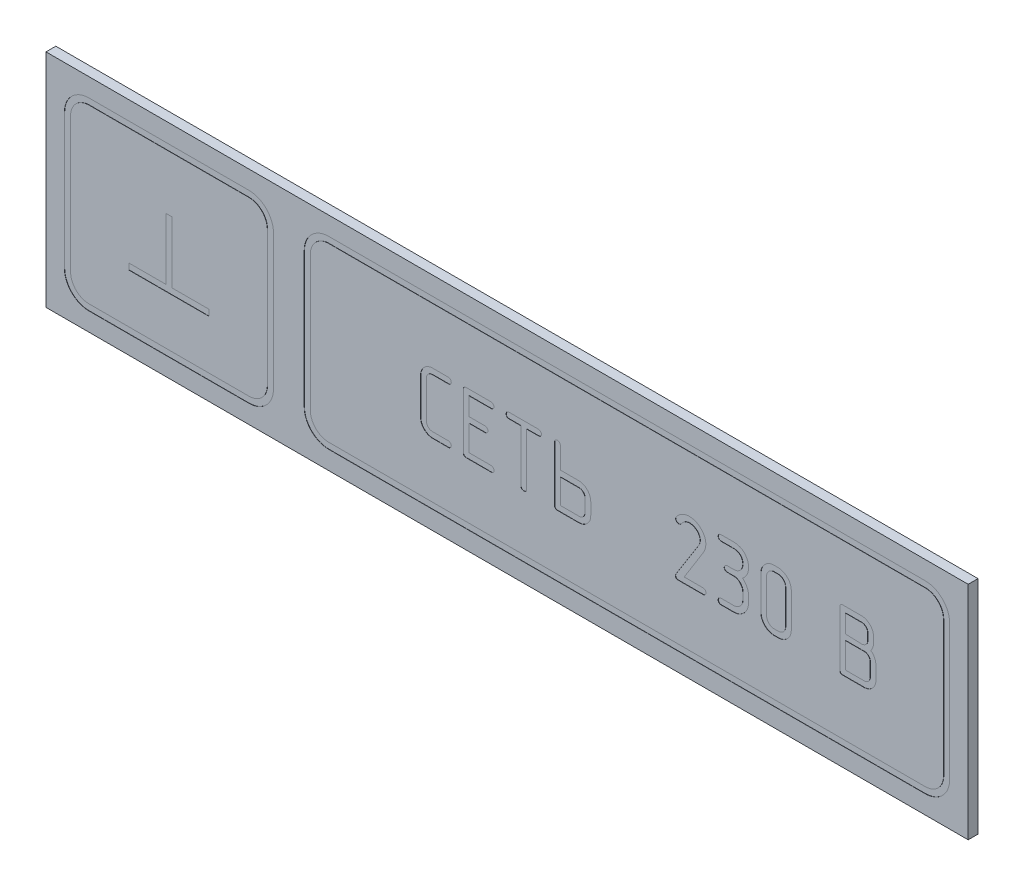
SolidWorks part; units mm, degrees
ref_plane "Спереди" through (0, 0, 0) normal (0, 0, 1) x (1, 0, 0)
ref_plane "Сверху" through (0, 0, 0) normal (0, 1, 0) x (1, 0, 0)
ref_plane "Справа" through (0, 0, 0) normal (1, 0, 0) x (0, 0, -1)
sketch "Эскиз1" plane through (0, 0, 0) normal (0, 0, 1) x (1, 0, 0)
  line L1 (0, 0) -> (75, 0)
  line L2 (0, 0) -> (0, 18)
  line L3 (0, 18) -> (75, 18)
  line L4 (75, 0) -> (75, 18)
  dimension "D1" = 75
  dimension "D2" = 18
extrude "Вытянуть1" add sketch "Эскиз1" along normal blind 0.8
sketch "Эскиз2" plane through (0, 0, 0.8) normal (0, 0, 1) x (1, 0, 0)
  line L0 (0, 0) -> (75, 0) construction
  line L1 (75, 0) -> (75, 18) construction
  text T0 "СЕТЬ  230 В" font "GOST type B" height 5
  dimension "D1" = 6.5
  dimension "D2" = 45
extrude "Вырез-Вытянуть1" cut sketch "Эскиз2" against normal blind 0.02
sketch "Эскиз3" plane through (0, 0, 0.8) normal (0, 0, 1) x (1, 0, 0)
  line L0 (10, 11.5) -> (10, 6.5)
  line L1 (0, 0) -> (75, 0) construction
  line L2 (0, 18) -> (0, 0) construction
  dimension "D1" = 5
  dimension "D2" = 6.5
  dimension "D3" = 10
extrude "Вырез-Вытянуть-Тонкостенный1" cut sketch "Эскиз3" against normal blind 0.02 and the other way blind 0.02 thin thin type mid plane wall 0.5
sketch "Эскиз4" plane through (0, 0, 0.8) normal (0, 0, 1) x (1, 0, 0)
  line L0 (6.75, 6.5) -> (13.25, 6.5)
  line L1 (0, 0) -> (75, 0) construction
  line L2 (9.75, 6.5) -> (9.75, 11.5) construction
  line L3 (10.25, 6.5) -> (10.25, 11.5) construction
  dimension "D1" = 6.5
  dimension "D2" = 3
  dimension "D3" = 3
extrude "Вырез-Вытянуть-Тонкостенный2" cut sketch "Эскиз4" against normal blind 0.02 and the other way blind 0.02 thin thin type one direction wall 0.5
sketch "Эскиз5" plane through (0, 0, 0.8) normal (0, 0, 1) x (1, 0, 0)
  line L0 (75, 18) -> (0, 18) construction
  line L1 (3.5, 2) -> (16.5, 2)
  line L2 (2, 3.5) -> (2, 14.5)
  line L3 (3.5, 16) -> (16.5, 16)
  line L4 (18, 3.5) -> (18, 14.5)
  line L6 (0, 18) -> (0, 0) construction
  arc A0 (2, 14.5) -> (3.5, 16) centre (3.5, 14.5) cw
  arc A1 (16.5, 16) -> (18, 14.5) centre (16.5, 14.5) cw
  arc A2 (16.5, 2) -> (18, 3.5) centre (16.5, 3.5) ccw
  arc A3 (3.5, 2) -> (2, 3.5) centre (3.5, 3.5) cw
  point P10 (2, 16)
  point P13 (18, 16)
  point P18 (2, 2)
  dimension "D5" = 1.5
  dimension "D1" = 14
  dimension "D2" = 16
  dimension "D3" = 2
  dimension "D4" = 2
extrude "Вырез-Вытянуть-Тонкостенный3" cut sketch "Эскиз5" against normal blind 0.02 and the other way blind 0.02 thin thin type one direction wall 0.5
sketch "Эскиз6" plane through (0, 0, 0.8) normal (0, 0, 1) x (1, 0, 0)
  line L0 (75, 0) -> (75, 18) construction
  line L1 (23, 2) -> (71.5, 2)
  line L2 (21.5, 3.5) -> (21.5, 14.5)
  line L3 (23, 16) -> (71.5, 16)
  line L4 (73, 3.5) -> (73, 14.5)
  line L5 (75, 18) -> (0, 18) construction
  line L6 (0, 0) -> (75, 0) construction
  line L7 (18.5, 14.5) -> (18.5, 3.5) construction
  arc A0 (21.5, 14.5) -> (23, 16) centre (23, 14.5) cw
  arc A1 (71.5, 16) -> (73, 14.5) centre (71.5, 14.5) cw
  arc A2 (71.5, 2) -> (73, 3.5) centre (71.5, 3.5) ccw
  arc A3 (23, 2) -> (21.5, 3.5) centre (23, 3.5) cw
  dimension "D5" = 1.5
  dimension "D1" = 2
  dimension "D2" = 2
  dimension "D3" = 2
  dimension "D4" = 3
extrude "Вырез-Вытянуть-Тонкостенный4" cut sketch "Эскиз6" against normal blind 0.02 and the other way blind 0.02 thin thin type one direction wall 0.5
